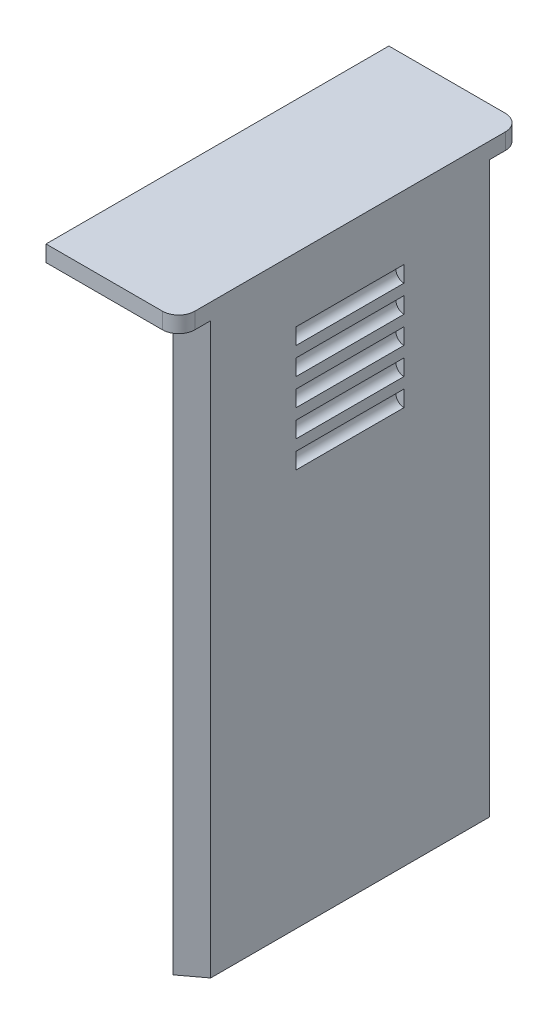
SolidWorks part; units mm, degrees
ref_plane "Alzado" through (0, 0, 0) normal (0, 0, 1) x (1, 0, 0)
ref_plane "Planta" through (0, 0, 0) normal (0, 1, 0) x (1, 0, 0)
ref_plane "Vista lateral" through (0, 0, 0) normal (1, 0, 0) x (0, 0, -1)
sketch "Croquis1" plane through (0, 111.4679, 0) normal (0, 1, 0) x (1, 0, 0)
  line L0 (-3.6522, -72.4184) -> (-15.9522, -72.4184)
  line L5 (-15.9522, -72.4184) -> (-15.9522, -104.2184)
  line L6 (-15.9522, -104.2184) -> (-3.6522, -104.2184)
  line L7 (-3.6522, -104.2184) -> (-3.6522, -72.4184)
  dimension "D1" = 12.3
  dimension "D2" = 31.8
extrude "Saliente-Extruir1" add sketch "Croquis1" against normal blind 1.5
sketch "Croquis2" plane through (0, 109.9679, 0) normal (0, -1, 0) x (1, 0, 0)
  line L0 (-3.6522, 101.2434) -> (-5.6522, 102.7434)
  line L3 (-3.6522, 104.2184) -> (-3.6522, 72.4184) construction
  line L4 (-15.9522, 88.3184) -> (1.8923, 88.3184) construction
  line L9 (-5.6522, 102.7434) -> (-5.6522, 73.8934)
  line L10 (-15.9522, 72.4184) -> (-15.9522, 104.2184) construction
  line L12 (-3.6522, 75.3934) -> (-3.6522, 101.2434)
  line L13 (-3.6522, 75.3934) -> (-5.6522, 73.8934)
  dimension "D1" = 53.13
  dimension "D2" = 2.5
  dimension "D3" = 28.85
extrude "Saliente-Extruir2" add sketch "Croquis2" along normal blind 52.8
ref_axis "Eje1" through (-3.6522, 111.4679, 88.3184) along (0, -1, 0)
ref_plane "Plano2" through (0, 0, 88.3184) normal (0, 0, 1) x (0, -1, 0)
sketch "Croquis4" plane through (0, 0, 88.3184) normal (0, 0, 1) x (0, -1, 0)
  line L0 (-104.7679, -3.6522) -> (-111.4679, -3.6522) construction
  line L1 (-111.4679, -3.6522) -> (-57.1679, -3.6522) construction
  circle A0 centre (-104.7679, -3.6522) radius 0.75
  circle A1 centre (-102.2679, -3.6522) radius 0.75
  circle A2 centre (-99.7679, -3.6522) radius 0.75
  circle A3 centre (-97.2679, -3.6522) radius 0.75
  circle A4 centre (-94.7679, -3.6522) radius 0.75
  dimension "D2" = 5
  dimension "D3" = 2.5
  dimension "D1" = 1.5
sketch "Croquis5" plane through (0, 109.9679, 0) normal (0, -1, 0) x (1, 0, 0)
  line L0 (-5.6522, 102.7434) -> (-5.6522, 73.8934) construction
  line L1 (-5.6522, 95.8184) -> (-6.6522, 95.8184)
  line L2 (-5.6522, 95.8184) -> (-5.6522, 80.8184)
  line L3 (-5.6522, 80.8184) -> (-6.6522, 80.8184)
  line L4 (-6.6522, 95.8184) -> (-6.6522, 80.8184)
  line L5 (-15.9522, 88.3184) -> (-5.6522, 88.3184) construction
  line L6 (-15.9522, 72.4184) -> (-15.9522, 104.2184) construction
  dimension "D1" = 15
  dimension "D2" = 1
extrude "Saliente-Extruir4" add sketch "Croquis5" along normal blind 20
extrude "Cortar-Extruir1" cut sketch "Croquis4" against normal mid plane 10
fillet "Redondeo1" radius 1.5 2 edges at (-3.6522, 110.7179, 72.4184) (-3.6522, 110.7179, 104.2184)
